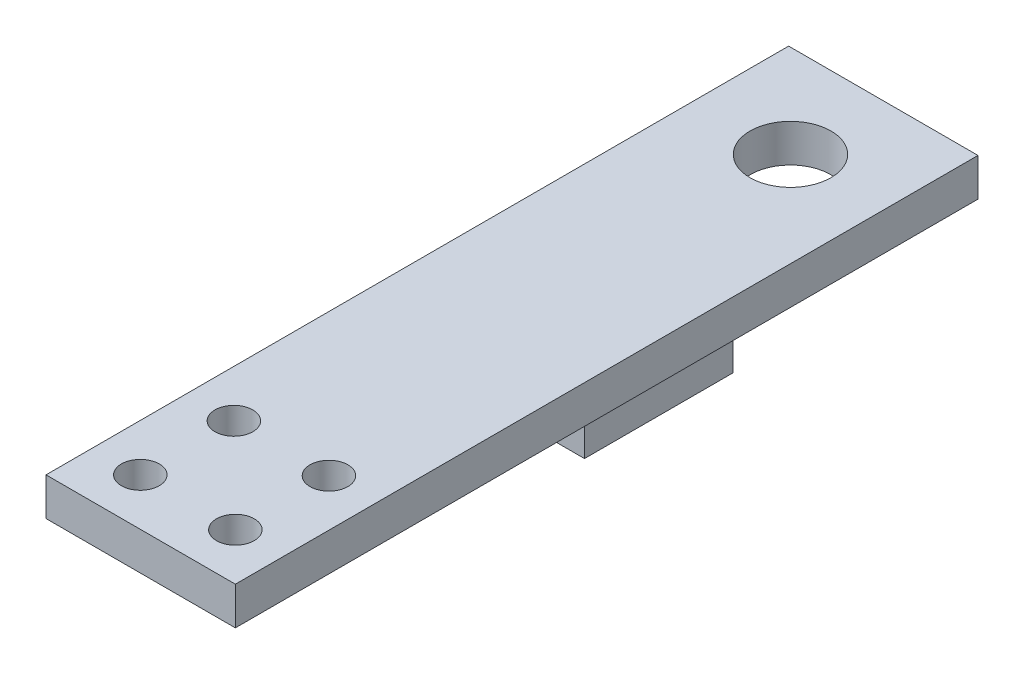
SolidWorks part; units mm, degrees
ref_plane "Front Plane" through (0, 0, 0) normal (0, 0, 1) x (1, 0, 0)
ref_plane "Top Plane" through (0, 0, 0) normal (0, 1, 0) x (1, 0, 0)
ref_plane "Right Plane" through (0, 0, 0) normal (1, 0, 0) x (0, 0, -1)
sketch "Sketch1" plane through (0, 0, 0) normal (0, 1, 0) x (1, 0, 0)
  line L0 (0, -10) -> (0, 10) construction
  line L1 (2.55, -10) -> (-2.55, -10)
  line L2 (2.55, -10) -> (2.55, 10)
  line L3 (2.55, 10) -> (-2.55, 10)
  line L4 (-2.55, -10) -> (-2.55, 10)
  line L5 (2.55, -10) -> (-2.55, 10) construction
  line L6 (2.55, 10) -> (-2.55, -10) construction
  line L7 (-1.8025, 2.15) -> (1.8025, 2.15) construction
  line L8 (-1.8025, 4.15) -> (1.8025, 4.15)
  line L9 (-1.8025, 4.15) -> (-1.8025, 0.15)
  line L10 (-1.8025, 0.15) -> (1.8025, 0.15)
  line L11 (1.8025, 4.15) -> (1.8025, 0.15)
  circle A0 centre (0, 7.5) radius 1.09
  circle A1 centre (-1.28, -6.21) radius 0.51
  circle A2 centre (-1.28, -8.73) radius 0.51
  circle A5 centre (1.28, -6.21) radius 0.51
  circle A6 centre (1.28, -8.73) radius 0.51
  point P0 (0, 0)
  point P9 (0, 0)
  point P11 (0, 4.15)
  point P26 (-7.5935, 0.15)
  point P27 (-5.372, -4.5536)
  point P28 (-4.8926, -8.5414)
  point P29 (-3.6746, -2.1777)
  point P30 (-1.1574, -8.6573)
  point P31 (0, 0)
  point P32 (0, 0)
  point P33 (0, 0)
  point P34 (0, 0)
  dimension "D3" = 2.18
  dimension "D8" = 1.02
  dimension "D1" = 5.1
  dimension "D2" = 20
  dimension "D4" = 2.5
  dimension "D5" = 12.15
  dimension "D6" = 4
  dimension "D7" = 3.605
  dimension "D9" = 1.27
  dimension "D10" = 1.27
  dimension "D11" = 2.52
extrude "Body" add sketch "Sketch1" along normal blind 1.02 contours L9 L8 L11 L10 | L2 L1 L4 L3 | A0 | A1 | A2 | A6 | A5
sketch "Sketch3" plane through (0, 1.02, 0) normal (0, 1, 0) x (1, 0, 0)
  line L0 (-1.8025, 0.15) -> (1.8025, 0.15) construction
  line L1 (-1.8025, 4.15) -> (-1.8025, 0.15) construction
  line L2 (-1.8025, 4.15) -> (1.8025, 4.15) construction
  line L3 (1.8025, 4.15) -> (1.8025, 0.15) construction
  line L4 (-1.8025, 0.15) -> (1.8025, 0.15)
  line L5 (-1.8025, 4.15) -> (-1.8025, 0.15)
  line L6 (-1.8025, 4.15) -> (1.8025, 4.15)
  line L7 (1.8025, 4.15) -> (1.8025, 0.15)
extrude "Sensor" add sketch "Sketch3" against normal blind 2.52
